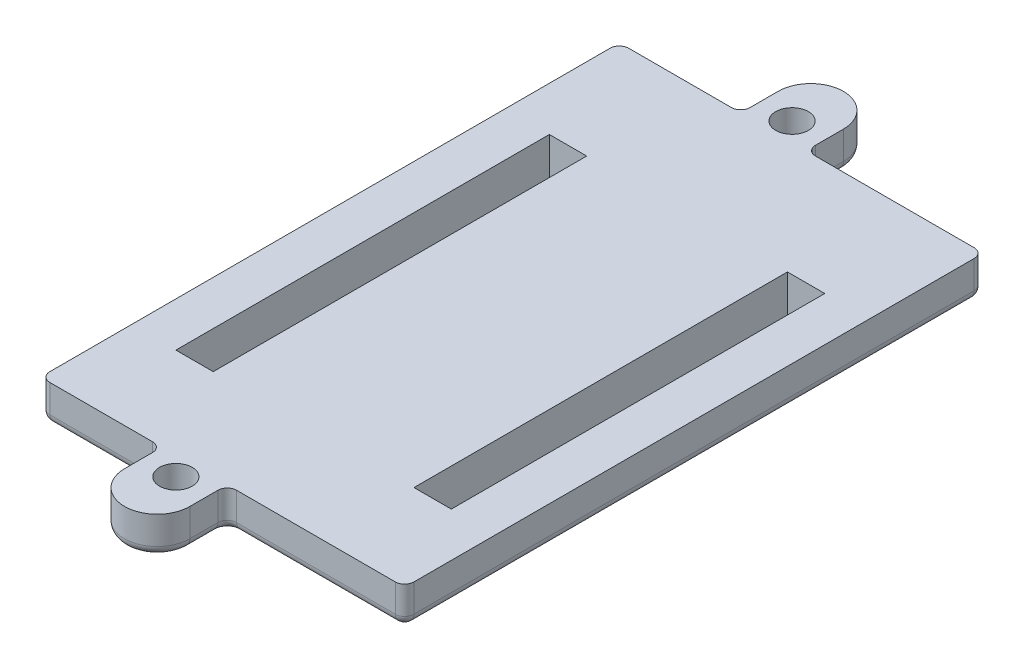
SolidWorks part; units mm, degrees
ref_plane "Front Plane" through (0, 0, 0) normal (0, 0, 1) x (1, 0, 0)
ref_plane "Top Plane" through (0, 0, 0) normal (0, 1, 0) x (1, 0, 0)
ref_plane "Right Plane" through (0, 0, 0) normal (1, 0, 0) x (0, 0, -1)
sketch "Sketch1" plane through (0, 0, 0) normal (0, 1, 0) x (1, 0, 0)
  line L0 (0, 31) -> (0, -31) construction
  line L1 (-19.5, 31) -> (19.5, 31)
  line L2 (-19.5, 31) -> (-19.5, -31)
  line L3 (-19.5, -31) -> (19.5, -31)
  line L4 (19.5, 31) -> (19.5, -31)
  line L5 (-19.5, 31) -> (19.5, -31) construction
  line L6 (-19.5, -31) -> (19.5, 31) construction
  line L7 (-14.75, 18.75) -> (-10.75, 18.75)
  line L8 (-14.75, 18.75) -> (-14.75, -21.25)
  line L9 (-14.75, -21.25) -> (-10.75, -21.25)
  line L10 (-10.75, 18.75) -> (-10.75, -21.25)
  line L11 (14.75, -21.25) -> (10.75, -21.25)
  line L12 (10.75, 18.75) -> (10.75, -21.25)
  line L13 (14.75, 18.75) -> (10.75, 18.75)
  line L14 (14.75, 18.75) -> (14.75, -21.25)
  line L15 (-19.5, 0) -> (19.5, 0) construction
  line L16 (0, -26) -> (0, 26) construction
  line L17 (-14.5, -26) -> (14.5, -26) construction
  line L18 (-14.5, -26) -> (-14.5, 26) construction
  line L19 (-14.5, 26) -> (14.5, 26) construction
  line L20 (14.5, -26) -> (14.5, 26) construction
  point P0 (0, 0)
  point P11 (-12.75, -21.25)
  point P26 (0, 0)
  dimension "D6" = 29
  dimension "D1" = 39
  dimension "D2" = 62
  dimension "D3" = 4
  dimension "D4" = 40
  dimension "D5" = 12.75
  dimension "D7" = 52
  dimension "D8" = 4.75
extrude "Base" add sketch "Sketch1" along normal blind 4
sketch "Sketch2" plane through (0, 0, 0) normal (0, 1, 0) x (1, 0, 0)
  line L0 (0, 0) -> (0, 29.13) construction
  line L1 (19.5, 31) -> (-19.5, 31) construction
  line L2 (-6.5, 31) -> (0.5, 31)
  line L3 (-6.5, 31) -> (-6.5, 35)
  line L4 (0.5, 31) -> (0.5, 35)
  line L5 (-19.5, 0) -> (19.5, 0) construction
  line L6 (-19.5, 31) -> (-19.5, -31) construction
  line L7 (19.5, -31) -> (19.5, 31) construction
  line L8 (-6.5, -31) -> (-6.5, -35)
  line L9 (-6.5, -31) -> (0.5, -31)
  line L10 (0.5, -31) -> (0.5, -35)
  circle A0 centre (-3, 33) radius 1.75
  arc A2 (-6.5, 35) -> (0.5, 35) centre (-3, 35) cw
  arc A3 (-6.5, -35) -> (0.5, -35) centre (-3, -35) ccw
  circle A4 centre (-3, -33) radius 1.75
  point P27 (-3, 31)
  dimension "D1" = 33
  dimension "D2" = 3.5
  dimension "D5" = 3
  dimension "D3" = 7
  dimension "D4" = 4
extrude "Mounting Ends" add sketch "Sketch2" along normal up to surface (4 mm away) up to face at (0, 4, 0)
fillet "1mm Edge Fillets" radius 1 20 edges at (-13, 0, 31) (10, 0, -31) (-6.5, 0, 33) (0.5, 0, -33) (-3, 0, 38.5) (-3, 0, -38.5) (0.5, 0, 33) (-6.5, 0, -33) (10, 0, 31) (19.5, 0, 0) (-13, 0, -31) (-19.5, 0, 0) (-19.5, 2, -31) (-6.5, 2, -31) (0.5, 2, -31) (19.5, 2, -31) (0.5, 2, 31) (-6.5, 2, 31) (19.5, 2, 31) (-19.5, 2, 31)
